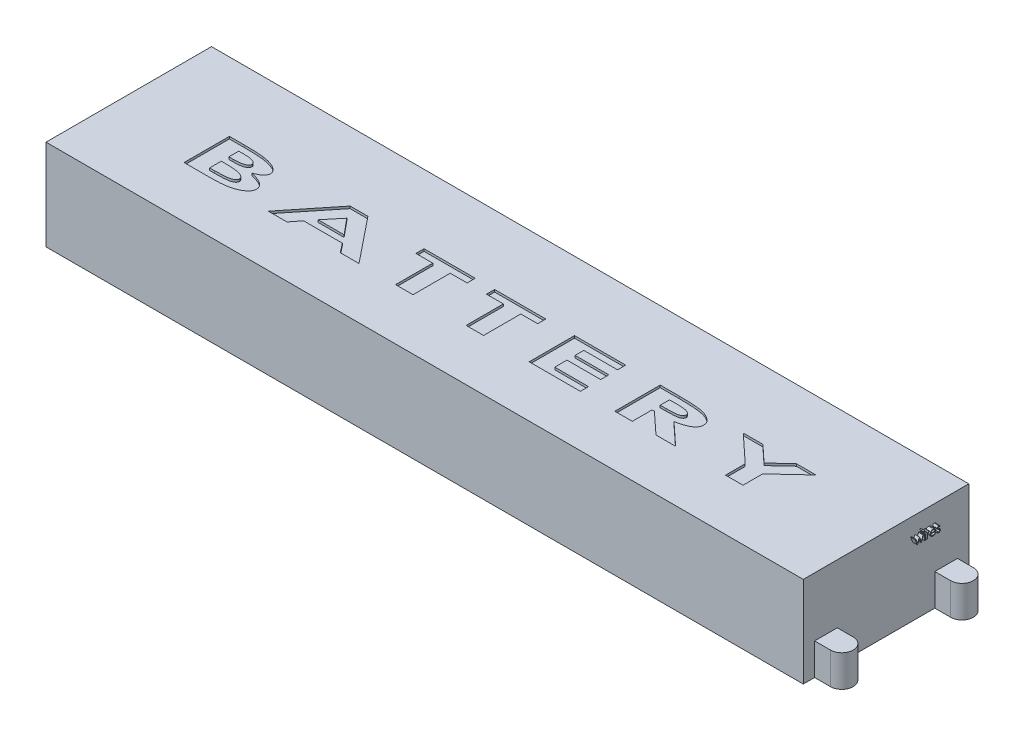
SolidWorks part; units mm, degrees
ref_plane "Front Plane" through (0, 0, 0) normal (0, 0, 1) x (1, 0, 0)
ref_plane "Top Plane" through (0, 0, 0) normal (0, 1, 0) x (1, 0, 0)
ref_plane "Right Plane" through (0, 0, 0) normal (1, 0, 0) x (0, 0, -1)
sketch "Sketch1" plane through (0, 0, 0) normal (0, 1, 0) x (1, 0, 0)
  line L1 (-167, 36.5) -> (167, 36.5)
  line L2 (-167, 36.5) -> (-167, -36.5)
  line L3 (-167, -36.5) -> (167, -36.5)
  line L4 (167, 36.5) -> (167, -36.5)
  line L5 (-167, 36.5) -> (167, -36.5) construction
  line L6 (-167, -36.5) -> (167, 36.5) construction
  point P0 (0, 0)
  dimension "D1" = 334
  dimension "D2" = 73
extrude "Boss-Extrude1" add sketch "Sketch1" along normal blind 40
sketch "Sketch4" plane through (0, 0, 0) normal (0, 1, 0) x (1, 0, 0)
  line L0 (167, -21.5) -> (174, -21.5)
  line L1 (167, -36.5) -> (167, 36.5) construction
  line L2 (167, -31.5) -> (174, -31.5)
  line L3 (-167, -36.5) -> (167, -36.5) construction
  line L4 (167, -31.5) -> (167, -21.5)
  arc A0 (174, -21.5) -> (174, -31.5) centre (174, -26.5) cw
  dimension "D1" = 5
  dimension "D2" = 7
  dimension "D3" = 5
extrude "Boss-Extrude3" add sketch "Sketch4" along normal blind 14
mirror "Mirror1" about plane through (0, 0, 0) normal (0, 0, 1) of "Boss-Extrude3"
sketch "Sketch2" plane through (167, 0, 0) normal (1, 0, 0) x (0, 0, -1)
  line L0 (6.5, 30) -> (26.5, 30) construction
  line L1 (36.5, 40) -> (36.5, 0) construction
  line L2 (-36.5, 40) -> (36.5, 40) construction
  text T0 "wires"
  dimension "D1" = 20
  dimension "D2" = 10
  dimension "D3" = 10
extrude "Boss-Extrude2" add sketch "Sketch2" along normal blind 2
sketch "Sketch3" plane through (0, 40, 0) normal (0, 1, 0) x (1, 0, 0)
  line L0 (-167, -13.8333) -> (167, -13.8333) construction
  line L1 (-167, 36.5) -> (-167, -36.5) construction
  line L2 (167, -36.5) -> (167, 36.5) construction
  line L3 (-167, -36.5) -> (167, -36.5) construction
  text T0 "<b>BATTERY</b>" font "Century Gothic" height 20
  dimension "D1" = 22.6667
extrude "Cut-Extrude1" cut sketch "Sketch3" against normal blind 1
